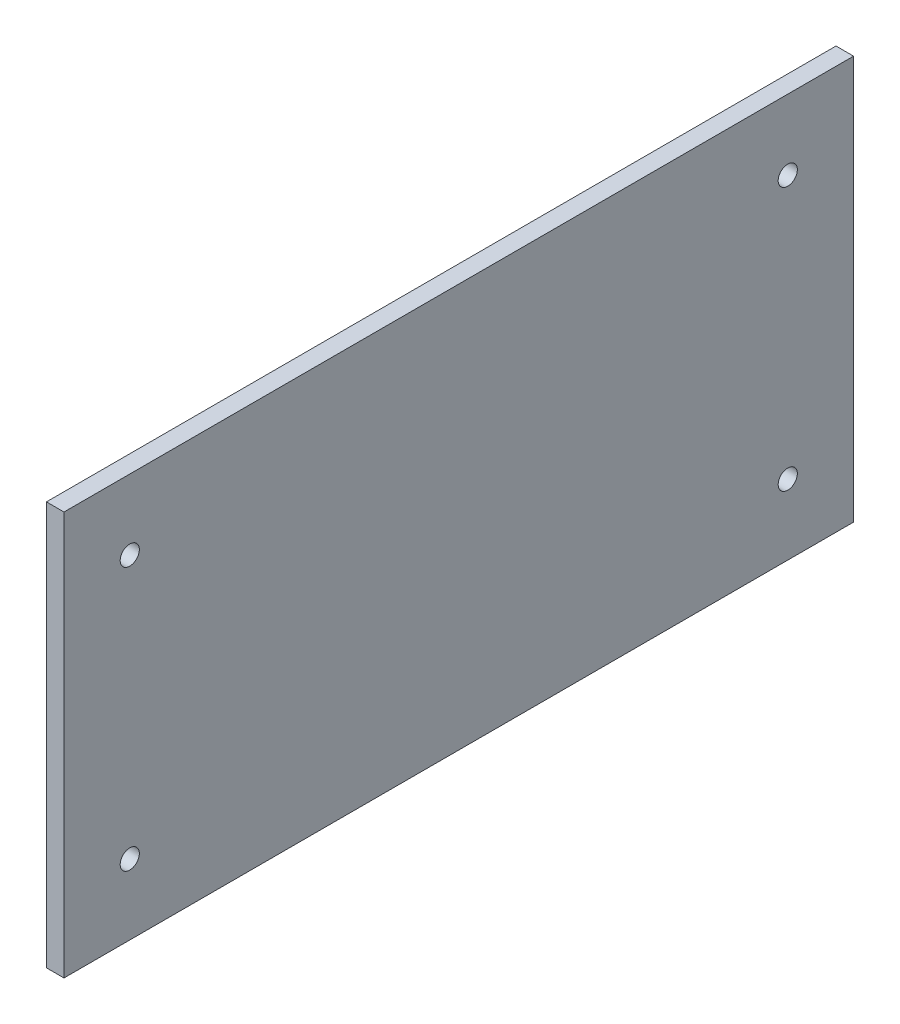
SolidWorks part; units mm, degrees
material "PCB (FR-4)"
ref_plane "Front Plane" through (0, 0, 0) normal (0, 0, 1) x (1, 0, 0)
ref_plane "Top Plane" through (0, 0, 0) normal (0, 1, 0) x (1, 0, 0)
ref_plane "Right Plane" through (0, 0, 0) normal (1, 0, 0) x (0, 0, -1)
sketch "Sketch1" plane through (0, 0, 0) normal (1, 0, 0) x (0, 0, -1)
  line L1 (-45, -23) -> (45, -23)
  line L2 (-45, -23) -> (-45, 23)
  line L3 (-45, 23) -> (45, 23)
  line L4 (45, -23) -> (45, 23)
  line L5 (-45, -23) -> (45, 23) construction
  line L6 (-45, 23) -> (45, -23) construction
  point P0 (0, 0)
  dimension "D1" = 46
  dimension "D2" = 90
extrude "Boss-Extrude1" add sketch "Sketch1" along normal blind 2
sketch "Sketch2" plane through (2, 0, 0) normal (1, 0, 0) x (0, 0, -1)
  line L0 (0, 0) -> (-37.5, 0) construction
  line L1 (-37.5, 0) -> (-37.5, -15) construction
  line L2 (0, 0) -> (37.5, 0) construction
  line L3 (37.5, 0) -> (37.5, 15) construction
  line L4 (37.5, 0) -> (37.5, -15) construction
  line L5 (-37.5, 0) -> (-37.5, 15) construction
  circle A0 centre (-37.5, -15) radius 1.0922
  circle A1 centre (37.5, -15) radius 1.0922
  circle A2 centre (37.5, 15) radius 1.0922
  circle A3 centre (-37.5, 15) radius 1.0922
  dimension "D3" = 2.1844
  dimension "D1" = 37.5
  dimension "D2" = 15
  dimension "D5" = 2
  dimension "D4" = 2
extrude "Cut-Extrude1" cut sketch "Sketch2" against normal blind 10
